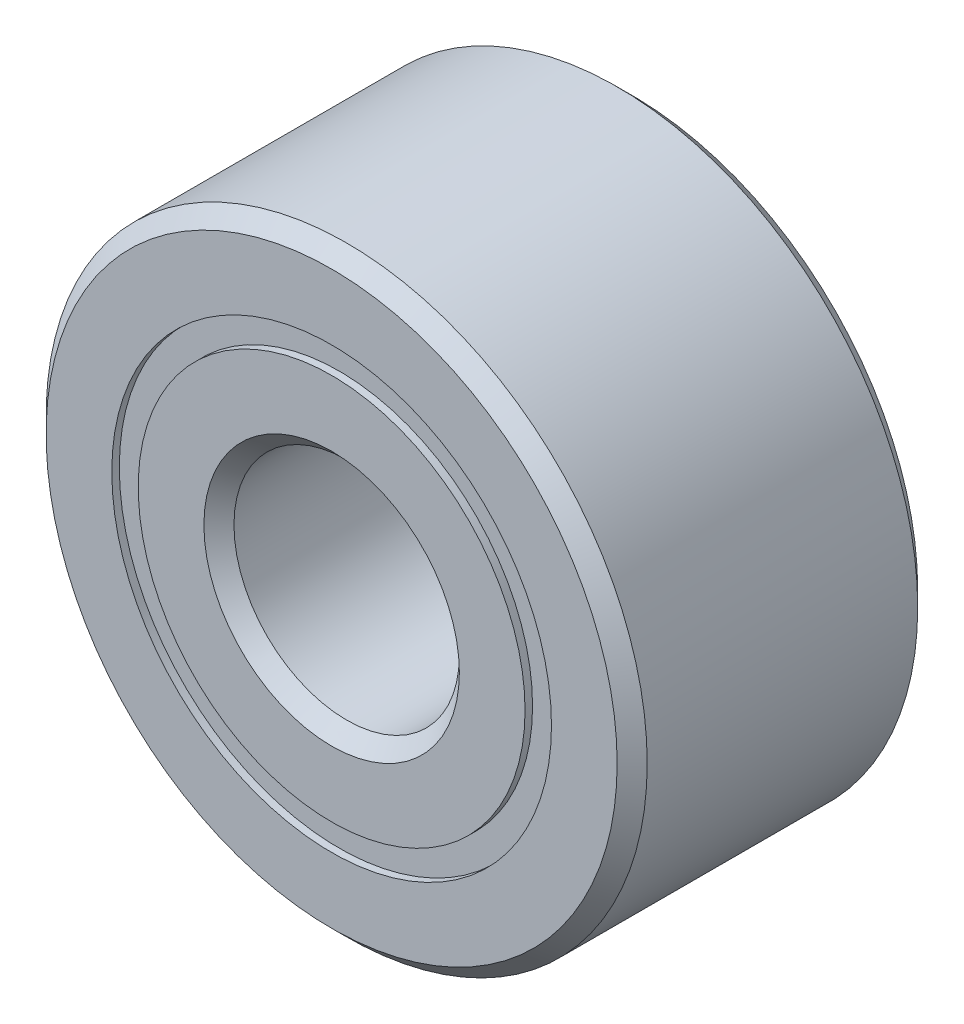
SolidWorks part; units mm, degrees
ref_plane "Front Plane" through (0, 0, 0) normal (0, 0, 1) x (1, 0, 0)
ref_plane "Top Plane" through (0, 0, 0) normal (0, 1, 0) x (1, 0, 0)
ref_plane "Right Plane" through (0, 0, 0) normal (1, 0, 0) x (0, 0, -1)
sketch "Sketch1" plane through (0, 0, 0) normal (1, 0, 0) x (0, 0, -1)
  line L0 (-2, 0) -> (2, 0) construction
  line L1 (0, 4) -> (0, -4) construction
  line L2 (1.8, 4) -> (-1.8, 4)
  line L3 (-1.8, 4) -> (-2, 3.8)
  line L4 (-2, 3.8) -> (-2, 2.9258)
  line L5 (-2, 2.9258) -> (-0.8889, 2.9258)
  line L6 (2, 2.9258) -> (0.8889, 2.9258)
  line L7 (2, 3.8) -> (2, 2.9258)
  line L8 (1.8, 4) -> (2, 3.8)
  line L9 (0, 4) -> (0, 2.75) construction
  line L10 (0, 2.75) -> (0, 1.5) construction
  arc A0 (-0.8889, 2.9258) -> (0.8889, 2.9258) centre (0, 2.75) cw
  point P14 (0, 1.5)
  dimension "Width" = 4
  dimension "OD" = 8
  dimension "D1" = 45
  dimension "D2" = 0.2
  dimension "Shaft Dia" = 3
  dimension "D3" = 1.7778
  dimension "D4" = 0.1758
revolve "Revolve1" add sketch "Sketch1" angle 360 about L0
sketch "Sketch3" plane through (0, 0, 0) normal (1, 0, 0) x (0, 0, -1)
  line L0 (-2, 2.5742) -> (-0.8889, 2.5742)
  line L1 (0, 4) -> (0, -4) construction
  line L2 (-2, 3.8) -> (-2, 2.9258) construction
  line L3 (-2, 2.5742) -> (-2, 1.7)
  line L4 (-1.8, 4) -> (-2, 3.8) construction
  line L5 (-2, 1.7) -> (-1.8, 1.5)
  line L6 (-1.8, 1.5) -> (1.8, 1.5)
  line L7 (1.8, 4) -> (1.8, -4) construction
  line L8 (1.8, 1.5) -> (2, 1.7)
  line L9 (2, -3.8) -> (2, 3.8) construction
  line L10 (2, 1.7) -> (2, 2.5742)
  line L11 (2, 2.5742) -> (0.8889, 2.5742)
  line L13 (1.8, 4) -> (2, 3.8) construction
  arc A0 (0.8889, 2.9258) -> (-0.8889, 2.9258) centre (0, 2.75) ccw construction
  arc A1 (0.8889, 2.5742) -> (-0.8889, 2.5742) centre (0, 2.75) cw
revolve "Revolve3" add sketch "Sketch3" angle 360 about L0
sketch "Sketch4" plane through (0, 0, 0) normal (1, 0, 0) x (0, 0, -1)
  line L0 (-0.9061, 2.75) -> (0.9061, 2.75)
  arc A2 (-0.9061, 2.75) -> (0.9061, 2.75) centre (0, 2.75) cw
  arc A3 (0.8889, 2.9258) -> (-0.8889, 2.9258) centre (0, 2.75) ccw construction
revolve "Revolve4" add sketch "Sketch4" angle 360 about L0
ref_axis "Axis1" through (0, 0, -2) along (0, 0, 1)
pattern_circular "CirPattern1" count 12 every 30 about axis through (0, 0, -2) along (0, 0, 1) of bodies 104
sketch "Sketch5" plane through (0, 0, 0) normal (1, 0, 0) x (0, 0, -1)
  line L0 (-2, 2.9258) -> (-0.8889, 2.9258) construction
  line L1 (-1.9, 2.9258) -> (-0.9061, 2.9258)
  line L2 (-1.9, 2.9258) -> (-1.9, 2.5742)
  line L3 (-1.9, 2.5742) -> (-0.9061, 2.5742)
  line L4 (-0.9061, 2.9258) -> (-0.9061, 2.5742)
  line L5 (-2, 2.5742) -> (-0.8889, 2.5742) construction
  line L6 (2, 2.9258) -> (0.8889, 2.9258) construction
  line L7 (1.9, 2.9258) -> (0.9061, 2.9258)
  line L8 (1.9, 2.9258) -> (1.9, 2.5742)
  line L9 (1.9, 2.5742) -> (0.9061, 2.5742)
  line L10 (0.9061, 2.9258) -> (0.9061, 2.5742)
  line L11 (2, 2.5742) -> (0.8889, 2.5742) construction
  line L12 (-1.8, 4) -> (-2, 3.8) construction
  point P18 (-1.9, 3.9)
revolve "Revolve5" add sketch "Sketch5" angle 360 about L0
sketch "Sketch6" plane through (0, 0, 0) normal (1, 0, 0) x (0, 0, -1)
  line L0 (2, 0) -> (-2, 0) construction
  line L1 (2, 2.9258) -> (0.9, 2.9258)
  line L2 (2, 2.9258) -> (2, 9.5)
  line L3 (2, 9.5) -> (0.9, 9.5)
  line L4 (0.9, 2.9258) -> (0.9, 9.5)
  dimension "Th" = 1.1
  dimension "Flange OD" = 19
revolve "Revolve6" [suppressed] add sketch "Sketch6" angle 360 about L0
equation "\"D2@Sketch1\" = \"Width@Sketch1\"*.05"
equation "\"D3@Sketch1\" = \"Width@Sketch1\"/2.25"
equation "\"D4@Sketch1\" = (((\"OD@Sketch1\"-\"Width@Sketch1\")/2)/3.25)/3.5"
equation "\"D2@CirPattern1\" = 360/\"Balls@CirPattern1\""
